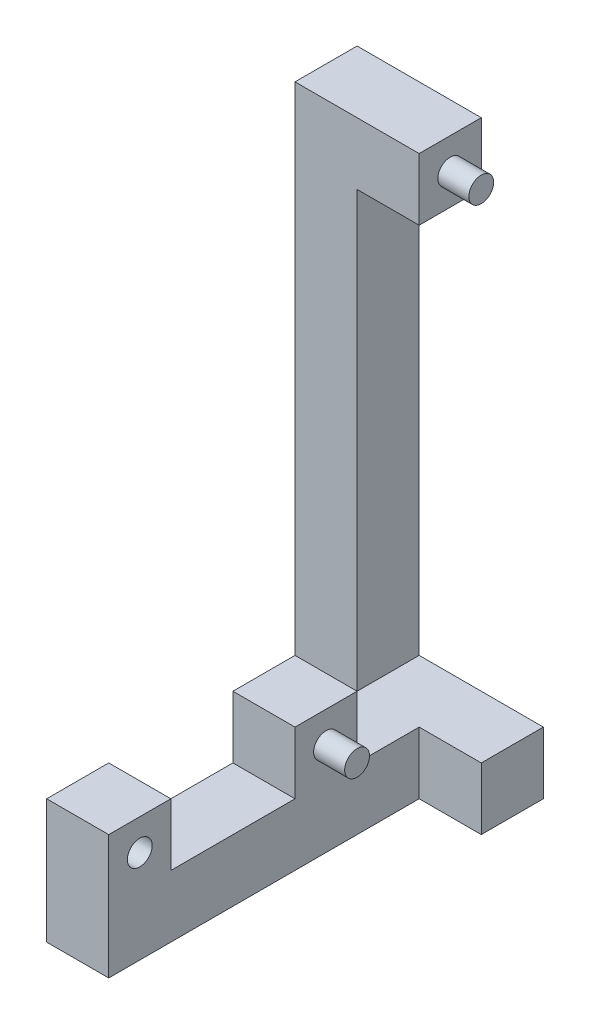
SolidWorks part; units mm, degrees
material "Hexcel AS4C (3000 Filaments)"
ref_plane "Front Plane" through (0, 0, 0) normal (0, 0, 1) x (1, 0, 0)
ref_plane "Top Plane" through (0, 0, 0) normal (0, 1, 0) x (1, 0, 0)
ref_plane "Right Plane" through (0, 0, 0) normal (1, 0, 0) x (0, 0, -1)
sketch "LowerBase" plane through (0, 0, 0) normal (1, 0, 0) x (0, 0, -1)
  line L9 (0, 0) -> (-1200, 0)
  line L10 (0, 0) -> (0, 200)
  line L11 (0, 200) -> (-1200, 200)
  line L12 (-1200, 0) -> (-1200, 200)
  line L13 (-1200, 200) -> (-1000, 200)
  line L14 (-1200, 200) -> (-1200, 400)
  line L15 (-1200, 400) -> (-1000, 400)
  line L16 (-1000, 200) -> (-1000, 400)
  line L17 (-600, 200) -> (-400, 200)
  line L18 (-600, 200) -> (-600, 400)
  line L19 (-600, 400) -> (-400, 400)
  line L20 (-400, 200) -> (-400, 400)
  dimension "D2" = 1200
  dimension "D1" = 200
  dimension "D3" = 200
  dimension "D4" = 200
  dimension "D5" = 200
  dimension "D6" = 200
  dimension "D7" = 400
  dimension "D8" = 400
extrude "Boss-Extrude1" add sketch "LowerBase" along normal blind 200 contours L12 L9 L10 L11 | L14 L15 L16 L13 | L19 L20 L17 L18
sketch "UpperBase" plane through (0, 0, 0) normal (1, 0, 0) x (0, 0, -1)
  line L1 (0, 0) -> (-200, 0)
  line L2 (0, 0) -> (0, 1800)
  line L3 (0, 1800) -> (-200, 1800)
  line L4 (-200, 0) -> (-200, 1800)
  dimension "D1" = 1800
  dimension "D2" = 200
extrude "Boss-Extrude2" add sketch "UpperBase" along direction (-1, 0, 0) on the side against the normal blind 200
sketch "TopPivot" plane through (0, 0, 0) normal (1, 0, 0) x (0, 0, -1)
  line L1 (-200, 1800) -> (0, 1800)
  line L2 (-200, 1800) -> (-200, 1600)
  line L3 (-200, 1600) -> (0, 1600)
  line L4 (0, 1800) -> (0, 1600)
  dimension "D1" = 200
  dimension "D2" = 200
extrude "Boss-Extrude3" add sketch "TopPivot" along normal blind 200
sketch "PressTable" plane through (0, 0, 0) normal (1, 0, 0) x (0, 0, -1)
  line L0 (0, 200) -> (-400, 200) construction
  line L1 (0, 0) -> (-200, 0)
  line L2 (0, 0) -> (0, 200)
  line L3 (0, 200) -> (-200, 200)
  line L4 (-200, 0) -> (-200, 200)
  dimension "D1" = 200
  dimension "D2" = 200
extrude "Boss-Extrude4" add sketch "PressTable" along normal blind 400
sketch "MiddleRivet" plane through (0, 0, 0) normal (1, 0, 0) x (0, 0, -1)
  line L0 (-600, 200) -> (-400, 400) construction
  circle A0 centre (-500, 300) radius 40
  dimension "D1" = 80
extrude "Boss-Extrude5" add sketch "MiddleRivet" along normal blind 300
sketch "TopRivet" plane through (0, 0, 0) normal (1, 0, 0) x (0, 0, -1)
  line L0 (0, 1800) -> (-200, 1600) construction
  circle A0 centre (-100, 1700) radius 40
  dimension "D1" = 80
extrude "Boss-Extrude6" add sketch "TopRivet" along normal blind 300
sketch "Sketch6" plane through (0, 0, 0) normal (1, 0, 0) x (0, 0, -1)
  line L0 (-1000, 400) -> (-1200, 200) construction
  line L1 (-1200, 0) -> (-1200, 400) construction
  circle A0 centre (-1100, 300) radius 40
  dimension "D1" = 80
extrude "Cut-Extrude1" cut sketch "Sketch6" against normal through all both and the other way through all
equation "\"baseFrameHeight\"= 180cm"
equation "\"baseFrameLength\"= 120cm"
equation "\"baseFrameThickness\"= 20cm"
equation "\"D2@LowerBase\" = \"baseFrameLength\""
equation "\"D1@LowerBase\" = \"baseFrameThickness\""
equation "\"D3@LowerBase\" = \"baseFrameThickness\""
equation "\"D4@LowerBase\" = \"baseFrameThickness\""
equation "\"D5@LowerBase\" = \"baseFrameThickness\""
equation "\"D6@LowerBase\" = \"baseFrameThickness\""
equation "\"D1@Boss-Extrude1\"=\"baseFrameThickness\""
equation "\"D1@UpperBase\" = \"baseFrameHeight\""
equation "\"D2@UpperBase\" = \"baseFrameThickness\""
equation "\"D1@Boss-Extrude2\"=\"baseFrameThickness\""
equation "\"D1@TopPivot\" = \"baseFrameThickness\""
equation "\"D2@TopPivot\" = \"baseFrameThickness\""
equation "\"D1@Boss-Extrude3\"=\"baseFrameThickness\""
equation "\"D2@PressTable\" = \"baseFrameThickness\""
equation "\"D1@Boss-Extrude4\"=2*\"baseFrameThickness\""
equation "\"D1@MiddleRivet\" = \"HoleMountDiameter@PrintingPress.Assembly\""
equation "\"D1@Boss-Extrude5\"=\"RivetLength@PrintingPress.sldasm\"+\"baseFrameThickness\""
equation "\"D1@TopRivet\" = \"HoleMountDiameter@PrintingPress.Assembly\""
equation "\"D1@Boss-Extrude6\" = \"RivetLength@PrintingPress.Assembly\" + \"baseFrameThickness\""
equation "\"D1@Sketch6\"=\"HoleMountDiameter@PrintingPress.sldasm\""
